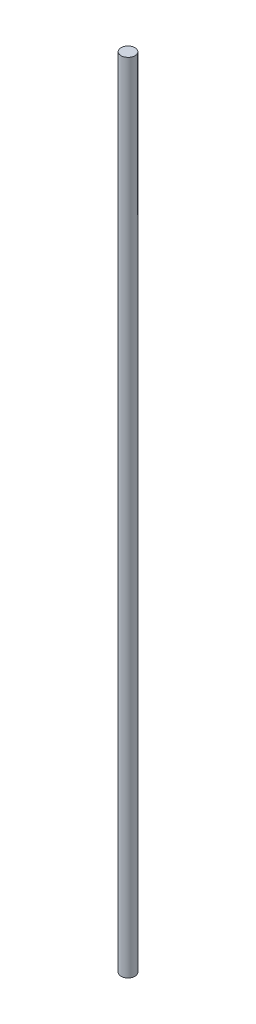
SolidWorks part; units mm, degrees
material "Chrome Stainless Steel"
ref_plane "Front Plane" through (0, 0, 0) normal (0, 0, 1) x (1, 0, 0)
ref_plane "Top Plane" through (0, 0, 0) normal (0, 1, 0) x (1, 0, 0)
ref_plane "Right Plane" through (0, 0, 0) normal (1, 0, 0) x (0, 0, -1)
sketch "Sketch1" plane through (0, 0, 0) normal (0, 1, 0) x (1, 0, 0)
  circle A0 centre (0, 0) radius 3.175
extrude "Boss-Extrude1" add sketch "Sketch1" along normal blind 364.01
